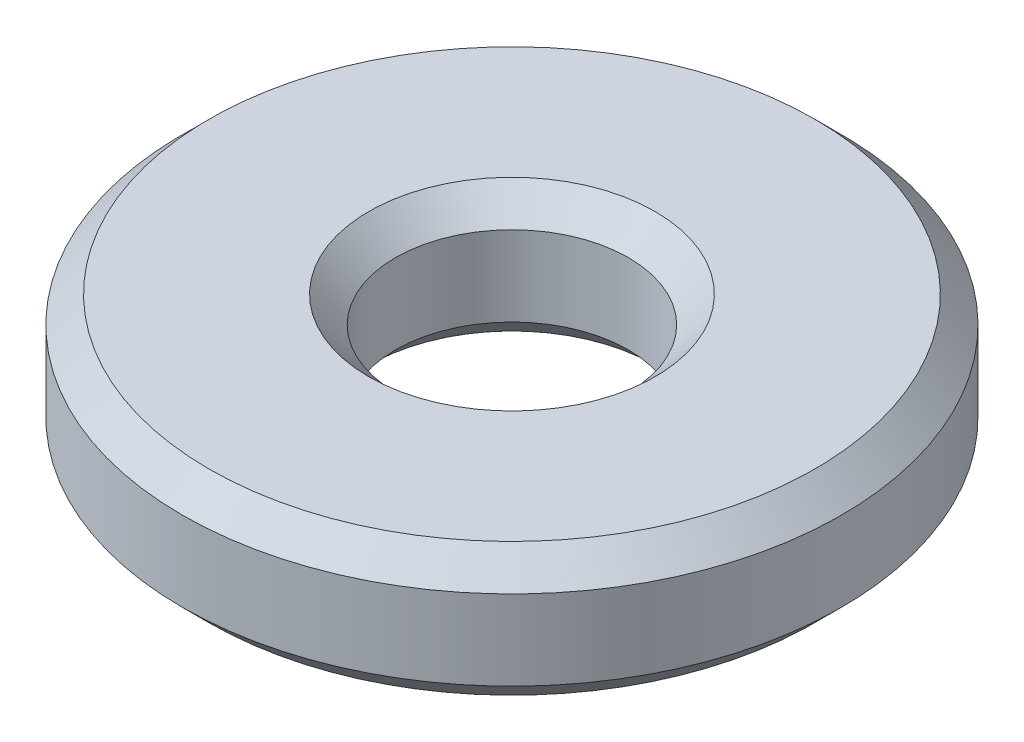
SolidWorks part; units mm, degrees
ref_plane "Front Plane" through (0, 0, 0) normal (0, 0, 1) x (1, 0, 0)
ref_plane "Top Plane" through (0, 0, 0) normal (0, 1, 0) x (1, 0, 0)
ref_plane "Right Plane" through (0, 0, 0) normal (1, 0, 0) x (0, 0, -1)
sketch "Sketch2" plane through (0, 0, 0) normal (0, 1, 0) x (1, 0, 0)
  circle A0 centre (0, 0) radius 1.75
  circle A1 centre (0, 0) radius 4.95
  dimension "D1" = 3.2
  dimension "D2" = 3.5
extrude "Boss-Extrude1" add sketch "Sketch2" along normal blind 2
chamfer "Chamfer1" distance 0.4 angle 45 4 edges at (0, 0, 4.95) (0, 0, 1.75) (0, 2, 4.95) (0, 2, 1.75)
